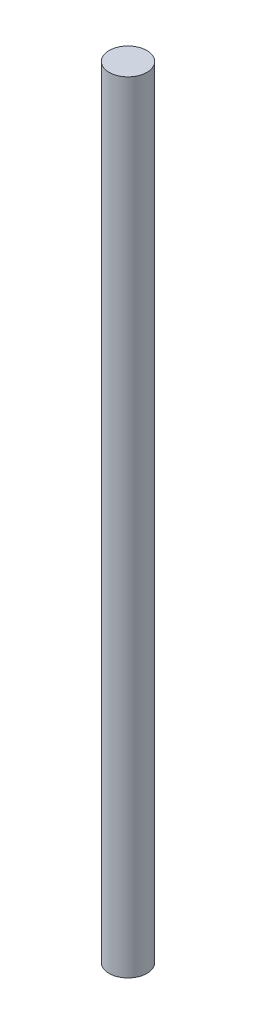
SolidWorks part; units mm, degrees
material "1023 Arkusz stali węglowej (SS)"
ref_plane "Płaszczyzna przednia" through (0, 0, 0) normal (0, 0, 1) x (1, 0, 0)
ref_plane "Płaszczyzna górna" through (0, 0, 0) normal (0, 1, 0) x (1, 0, 0)
ref_plane "Płaszczyzna prawa" through (0, 0, 0) normal (1, 0, 0) x (0, 0, -1)
sketch "Szkic1" plane through (0, 0, 0) normal (0, 1, 0) x (1, 0, 0)
  circle A0 centre (0, 0) radius 6
  dimension "D1" = 12
extrude "Dodanie-wyciągnięcie1" add sketch "Szkic1" along normal blind 247.55 contours A0
